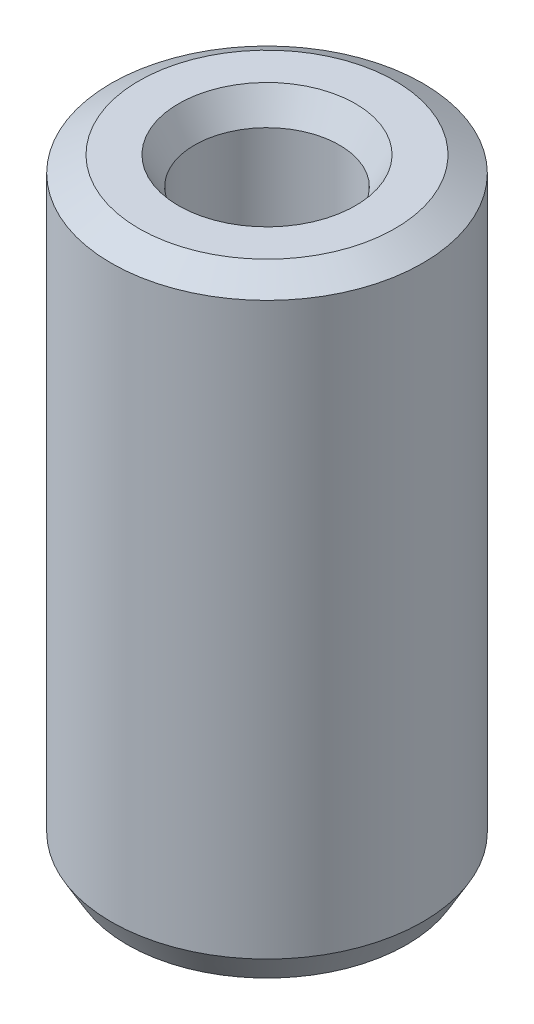
SolidWorks part; units mm, degrees
ref_plane "Front Plane" through (0, 0, 0) normal (0, 0, 1) x (1, 0, 0)
ref_plane "Top Plane" through (0, 0, 0) normal (0, 1, 0) x (1, 0, 0)
ref_plane "Right Plane" through (0, 0, 0) normal (1, 0, 0) x (0, 0, -1)
sketch "Sketch1" plane through (0, 0, 0) normal (0, 1, 0) x (1, 0, 0)
  circle A0 centre (0, 0) radius 5
  dimension "SLEEVE_OD" = 10
extrude "Boss-Extrude1" add sketch "Sketch1" along normal blind 19.7142
sketch "Sketch2" plane through (0, 0, 0) normal (0, 1, 0) x (1, 0, 0)
  circle A0 centre (0, 0) radius 2.3236
  dimension "BORE_D" = 4.6472
extrude "Cut-Extrude1" cut sketch "Sketch2" along normal through all
chamfer "Chamfer1" distance 0.5149 angle 60 4 edges at (0, 19.7142, 2.3236) (0, 0, 2.3236) (0, 0, 5) (0, 19.7142, 5) first distance on face at (0, 19.7142, 2.3236) first distance on face at (0, 0, 2.3236) first distance on face at (0, 19.7142, 5)
